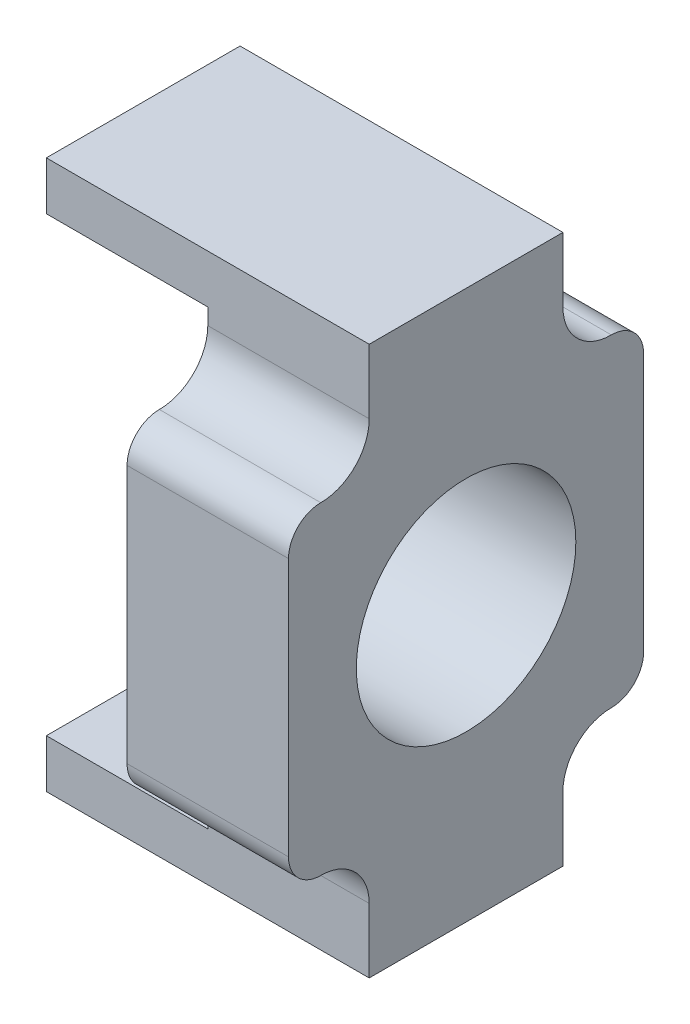
SolidWorks part; units mm, degrees
ref_plane "Front Plane" through (0, 0, 0) normal (0, 0, 1) x (1, 0, 0)
ref_plane "Top Plane" through (0, 0, 0) normal (0, 1, 0) x (1, 0, 0)
ref_plane "Right Plane" through (0, 0, 0) normal (1, 0, 0) x (0, 0, -1)
sketch "Sketch1" plane through (0, 0, 0) normal (1, 0, 0) x (0, 0, -1)
  line L1 (2.5, 0) -> (8.5, 0)
  line L2 (0, 3.5) -> (0, 13.5)
  line L3 (2.5, 17) -> (8.5, 17)
  line L4 (11, 3.5) -> (11, 13.5)
  line L7 (11, 13.5) -> (8.5, 13.5)
  line L8 (8.5, 17) -> (8.5, 13.5)
  line L11 (0, 13.5) -> (2.5, 13.5)
  line L12 (2.5, 17) -> (2.5, 13.5)
  line L15 (0, 3.5) -> (2.5, 3.5)
  line L16 (2.5, 0) -> (2.5, 3.5)
  line L19 (11, 3.5) -> (8.5, 3.5)
  line L20 (8.5, 0) -> (8.5, 3.5)
  circle A0 centre (5.5, 8.5) radius 3.4
  point P7 (0, 8.5)
  point P8 (5.5, 0)
  dimension "D1" = 6.8
  dimension "D2" = 11
  dimension "D3" = 17
  dimension "D5" = 3.5
  dimension "D6" = 3.5
  dimension "D7" = 6
extrude "Boss-Extrude1" add sketch "Sketch1" along normal blind 5
sketch "Sketch3" plane through (0, 0, 0) normal (-1, 0, 0) x (0, 0, 1)
  line L0 (-2.5, 3.5) -> (-2.5, 0) construction
  line L1 (-8.5, 17) -> (-2.5, 17)
  line L2 (-8.5, 17) -> (-8.5, 15.5)
  line L3 (-8.5, 15.5) -> (-2.5, 15.5)
  line L4 (-2.5, 17) -> (-2.5, 15.5)
  line L6 (-2.5, 0) -> (-8.5, 0)
  line L7 (-2.5, 0) -> (-2.5, 1.5)
  line L8 (-2.5, 1.5) -> (-8.5, 1.5)
  line L9 (-8.5, 0) -> (-8.5, 1.5)
  line L10 (-8.5, 17) -> (-2.5, 17) construction
  line L11 (-2.5, 0) -> (-8.5, 0) construction
  point P5 (-5.5, 0)
  point P6 (-5.5, 17)
  dimension "D1" = 1.5
extrude "Boss-Extrude2" add sketch "Sketch3" along normal blind 5
fillet "Fillet2" radius 1.5 4 edges at (2.5, 13.5, -8.5) (2.5, 13.5, -2.5) (2.5, 3.5, -2.5) (2.5, 3.5, -8.5)
fillet "Fillet3" radius 1 4 edges at (2.5, 3.5, -11) (2.5, 3.5, 0) (2.5, 13.5, 0) (2.5, 13.5, -11)
